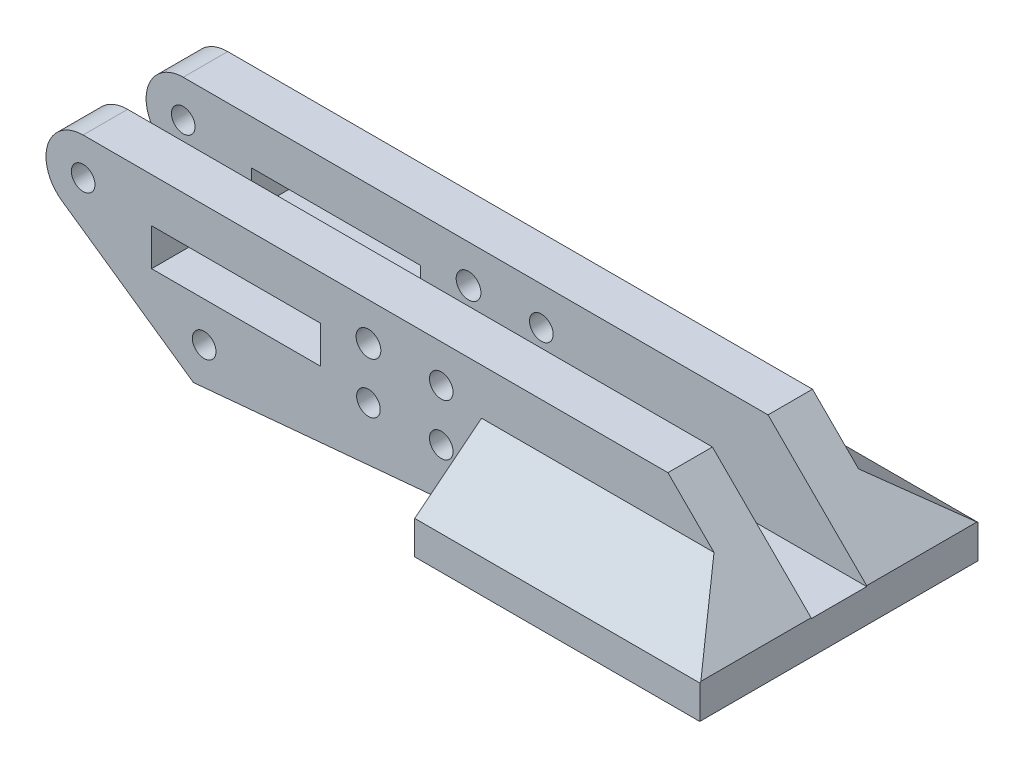
SolidWorks part; units mm, degrees
ref_plane "Plano frontal" through (0, 0, 0) normal (0, 0, 1) x (1, 0, 0)
ref_plane "Plano superior" through (0, 0, 0) normal (0, 1, 0) x (1, 0, 0)
ref_plane "Plano direito" through (0, 0, 0) normal (1, 0, 0) x (0, 0, -1)
ref_plane "Plano1" through (0, 0, 8) normal (0, 0, 1) x (1, 0, 0)
sketch "Esboço1" plane through (0, 0, 8) normal (0, 0, 1) x (1, 0, 0)
  line L0 (-36.1103, -64.7277) -> (-36.1103, 0)
  line L1 (-36.1103, 0) -> (-107.7561, 0)
  line L2 (-111.5734, -12.158) -> (-36.1103, -64.7277)
  arc A0 (-107.7561, 0) -> (-111.5734, -12.158) centre (-107.7561, -6.6783) ccw
extrude "Ressalto-extrusão1" add sketch "Esboço1" against normal blind 8
sketch "Esboço2" plane through (-36.1103, 0, 0) normal (1, 0, 0) x (0, 0, -1)
  line L0 (0, 0) -> (0, -23.8751)
  line L1 (0, -64.7277) -> (-18, -64.7277)
  line L2 (-18, -23.8751) -> (-18, -17.8751)
  line L3 (-18, 0) -> (0, 0)
  spline S0 degree 3 poles (0, -64.7277) (0, -51.1101) (0, -37.4926) (0, -23.8751) knots 0 0 0 0 1 1 1 1
  spline S1 degree 3 poles (-18, -64.7277) (-18, -51.1101) (-18, -37.4926) (-18, -23.8751) knots 0 0 0 0 1 1 1 1
  spline S2 degree 3 poles (-18, -17.7231) (-18, -17.7738) (-18, -17.8244) (-18, -17.8751) knots 0 0 0 0 1 1 1 1
  spline S3 degree 3 poles (-18, 0) (-18, -5.9077) (-18, -11.8154) (-18, -17.7231) knots 0 0 0 0 1 1 1 1
extrude "Ressalto-extrusão2" add sketch "Esboço2" along normal blind 51.2681
sketch "Esboço3" plane through (0, 0, 0) normal (0, 0, -1) x (-1, 0, 0)
  line L0 (-15.1579, 0) -> (-15.1579, -17.7231)
  line L1 (-15.1579, -17.7231) -> (2.5857, 0)
  line L2 (2.5857, 0) -> (-15.1579, 0)
extrude "Corte-extrusão1" cut sketch "Esboço3" against normal blind 8
sketch "Esboço4" plane through (0, 0, 0) normal (0, 1, 0) x (-1, 0, 0)
  line L0 (-15.1578, 18) -> (-15.1578, 8)
  line L1 (-15.1578, 8) -> (36.1103, 8)
  line L2 (36.1103, 8) -> (36.1103, 18)
  line L3 (36.1103, 18) -> (-15.1578, 18)
extrude "Corte-extrusão2" cut sketch "Esboço4" against normal blind 17.7231
sketch "Esboço5" plane through (0, -64.7277, 0) normal (0, -1, 0) x (1, 0, 0)
  line L0 (15.1578, 18) -> (-36.1103, 18)
  line L1 (-36.1103, 18) -> (-36.1103, 8)
  line L2 (-36.1103, 8) -> (-36.1103, 0)
  line L3 (-36.1103, 0) -> (15.1578, 0)
  line L4 (15.1578, 0) -> (15.1578, 18)
extrude "Corte-extrusão3" cut sketch "Esboço5" against normal blind 40.8526
sketch "Esboço6" plane through (0, -17.7231, 0) normal (0, 1, 0) x (-1, 0, 0)
  line L0 (-15.1578, 18) -> (-15.1578, 8)
  line L1 (-15.1578, 8) -> (36.1103, 8)
  line L2 (36.1103, 8) -> (36.1103, 18)
  line L3 (36.1103, 18) -> (-15.1578, 18)
extrude "Corte-extrusão4" cut sketch "Esboço6" against normal blind 0.152
sketch "Esboço7" plane through (0, 0, 18) normal (0, 0, 1) x (1, 0, 0)
  line L0 (-36.1103, -23.8751) -> (-36.1103, -64.7277)
  line L1 (-36.1103, -64.7277) -> (-111.5734, -12.158)
  line L2 (-107.7561, 0) -> (-2.5857, 0)
  line L3 (-2.5857, 0) -> (5.699, -8.2751)
  line L4 (5.699, -8.2751) -> (15.1578, -17.7231)
  line L5 (15.1578, -17.7231) -> (15.1578, -23.8751)
  line L6 (15.1578, -23.8751) -> (-36.1103, -23.8751)
  arc A0 (-111.5734, -12.158) -> (-107.7561, 0) centre (-107.7561, -6.6783) cw
extrude "Ressalto-extrusão3" add sketch "Esboço7" along normal blind 8
sketch "Esboço8" plane through (0, 0, 0) normal (0, 0, -1) x (-1, 0, 0)
  line L0 (36.1103, -8.2751) -> (36.1103, -23.8751)
  line L1 (36.1103, -23.8751) -> (-15.1578, -23.8751)
  line L2 (-15.1578, -23.8751) -> (-15.1578, -17.7231)
  line L3 (-15.1578, -17.7231) -> (-5.699, -8.2751)
  line L4 (-5.699, -8.2751) -> (36.1103, -8.2751)
extrude "Ressalto-extrusão4" add sketch "Esboço8" along normal blind 12.0172
sketch "Esboço9" plane through (0, 0, 26) normal (0, 0, 1) x (1, 0, 0)
  line L0 (15.1578, -17.7231) -> (15.1578, -23.8751)
  line L1 (15.1578, -23.8751) -> (-36.1103, -23.8751)
  line L2 (-36.1103, -23.8751) -> (-36.1103, -8.2751)
  line L3 (-36.1103, -8.2751) -> (5.699, -8.2751)
  line L4 (5.699, -8.2751) -> (15.1578, -17.7231)
extrude "Ressalto-extrusão5" add sketch "Esboço9" along normal blind 12.0172
sketch "Esboço10" plane through (0, 0, 8) normal (0, 0, 1) x (1, 0, 0)
  line L0 (-95.4438, -7.9723) -> (-95.4438, -14.6622)
  line L1 (-95.4438, -14.6622) -> (-65.0524, -14.6622)
  line L2 (-65.0524, -14.6622) -> (-65.0524, -7.9723)
  line L3 (-65.0524, -7.9723) -> (-95.4438, -7.9723)
extrude "Corte-extrusão5" cut sketch "Esboço10" against normal through all
sketch "Esboço11" plane through (0, 0, 18) normal (0, 0, -1) x (-1, 0, 0)
  line L0 (95.4438, -14.6622) -> (95.4438, -7.9723)
  line L1 (95.4438, -7.9723) -> (65.0524, -7.9723)
  line L2 (65.0524, -7.9723) -> (65.0524, -14.6622)
  line L3 (65.0524, -14.6622) -> (95.4438, -14.6622)
extrude "Corte-extrusão6" cut sketch "Esboço11" against normal through all
sketch "Esboço12" plane through (0, -23.8751, 0) normal (0, -1, 0) x (1, 0, 0)
  line L0 (-33.3603, -9.2672) -> (12.4079, -9.2672)
  line L1 (12.4079, -9.2672) -> (12.4079, 35.2672)
  line L2 (12.4079, 35.2672) -> (-33.3603, 35.2672)
  line L3 (-33.3603, 35.2672) -> (-33.3603, -9.2672)
extrude "Corte-extrusão7" cut sketch "Esboço12" against normal blind 3.15
draft "Inclinação1" type of draft neutral plane draft angle 38.62 faces to draft 1 face at (-9.9795, -8.2751, 33.5108) neutral plane through (-107.7561, -6.6783, 26) neutral plane normal (0, 0, 1) parameters "D1"=38.62
draft "Inclinação2" type of draft neutral plane draft angle 38.62 faces to draft 1 face at (-20.4318, -8.2751, -7.5108) neutral plane through (-107.7561, -6.6783, 0) neutral plane normal (0, 0, -1) parameters "D1"=38.62
draft "Inclinação3" type of draft neutral plane draft angle 84.752 faces to draft 2 face at (-36.1103, -49.408, 3) face at (-36.1103, -44.3014, 22) neutral plane through (0, -23.8751, 0) neutral plane normal (0, -1, 0) parameters "D1"=84.752
hole_wizard "Furo com folga de M41" positions "Esboço14" profile "Esboço13" hole size "M4" standard "Ansi Metric"
sketch "Esboço14" plane through (0, 0, 26) normal (0, 0, 1) x (1, 0, 0)
  point P0 (-56.4445, -6.7986)
sketch "Esboço13" plane through (-56.4445, -6.7986, 26) normal (1, 0, 0) x (0, -1, 0)
  line L0 (0, 0) -> (0, 8)
  line L1 (0, 8) -> (2.2264, 8)
  line L2 (2.2264, 8) -> (2.2264, 0)
  line L5 (2.2264, 0) -> (0, 0)
  line L11 (0, -6.35) -> (0, 107.95) construction
  dimension "Thru Hole Dia." = 4.4528
  dimension "Thru Hole Depth" = 8
hole_wizard "Furo de diâmetro Ø4.2 (4.2)1" positions "Esboço16" profile "Esboço15" hole size "Ø4.2" standard "Ansi Metric"
sketch "Esboço16" plane through (0, 0, 26) normal (0, 0, 1) x (1, 0, 0)
  point P0 (-85.9906, -21.8066)
  point P1 (-107.7561, -6.6783)
  point P2 (-43.3506, -6.7986)
  point P3 (-56.4445, -16.0521)
  point P4 (-43.3506, -16.0521)
sketch "Esboço15" plane through (-85.9906, -21.8066, 26) normal (1, 0, 0) x (0, -1, 0)
  line L0 (0, 0) -> (0, 8)
  line L1 (0, 8) -> (2.1, 8)
  line L2 (2.1, 8) -> (2.1, 0)
  line L5 (2.1, 0) -> (0, 0)
  line L11 (0, -6.35) -> (0, 107.95) construction
  dimension "Thru Hole Dia." = 4.2
  dimension "Thru Hole Depth" = 8
hole_wizard "Furo com folga de M42" positions "Esboço18" profile "Esboço17" hole size "M4" standard "Ansi Metric"
sketch "Esboço18" plane through (0, 0, 0) normal (0, 0, -1) x (-1, 0, 0)
  point P0 (56.4445, -6.7986)
sketch "Esboço17" plane through (-56.4445, -6.7986, 0) normal (1, 0, 0) x (0, 1, 0)
  line L0 (0, 0) -> (0, 38.0172)
  line L1 (0, 38.0172) -> (2.2264, 38.0172)
  line L2 (2.2264, 38.0172) -> (2.2264, 0)
  line L5 (2.2264, 0) -> (0, 0)
  line L11 (0, -6.35) -> (0, 107.95) construction
  dimension "Thru Hole Dia." = 4.4528
  dimension "Thru Hole Depth" = 38.0172
hole_wizard "Furo1" positions "Esboço20" profile "Esboço19" legacy
sketch "Esboço20" plane through (0, 0, 0) normal (0, 0, -1) x (-1, 0, 0)
  point P0 (43.3506, -16.0521)
  point P1 (56.4445, -16.0521)
  point P2 (43.3506, -6.7986)
  point P3 (107.7561, -6.6783)
  point P4 (85.9906, -21.8066)
sketch "Esboço19" plane through (-43.3506, -16.0521, 0) normal (1, 0, 0) x (0, 1, 0)
  line L0 (0, 0) -> (0, 38.0172)
  line L1 (0, 38.0172) -> (2.1232, 38.0172)
  line L2 (2.1232, 38.0172) -> (2.1232, 0)
  line L3 (2.1232, 0) -> (0, 0)
  line L4 (0, 110) -> (0, -10) construction
  dimension "Diameter" = 4.2464
  dimension "Depth" = 38.0172
